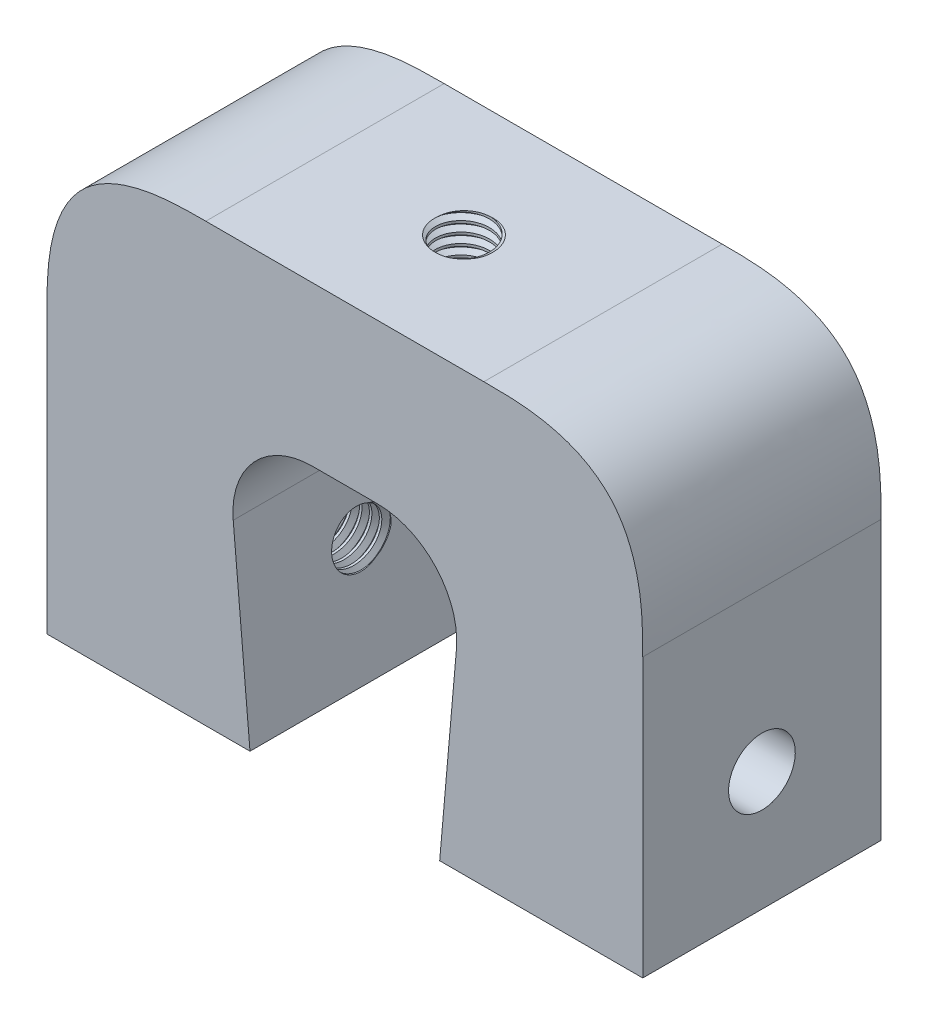
SolidWorks part; units mm, degrees
ref_plane "Front Plane" through (0, 0, 0) normal (0, 0, 1) x (1, 0, 0)
ref_plane "Top Plane" through (0, 0, 0) normal (0, 1, 0) x (1, 0, 0)
ref_plane "Right Plane" through (0, 0, 0) normal (1, 0, 0) x (0, 0, -1)
sketch "Sketch2" plane through (0, 0, 0) normal (0, 0, 1) x (1, 0, 0)
  line L0 (11.9379, -27.5) -> (37.5, -27.5)
  line L1 (-37.5, 27.5) -> (37.5, 27.5)
  line L2 (-37.5, 27.5) -> (-37.5, -27.5)
  line L3 (-37.5, -27.5) -> (-11.9379, -27.5)
  line L4 (37.5, 27.5) -> (37.5, -27.5)
  line L5 (-37.5, 27.5) -> (37.5, -27.5) construction
  line L6 (-37.5, -27.5) -> (37.5, 27.5) construction
  line L8 (-11.9379, -27.5) -> (-15, 7.5)
  line L9 (-15, 7.5) -> (15, 7.5)
  line L10 (11.9379, -27.5) -> (15, 7.5)
  line L13 (0, 0) -> (0, 7.5) construction
  point P0 (0, 0)
  dimension "D1" = 5
  dimension "D2" = 35
  dimension "D3" = 55
  dimension "D4" = 75
  dimension "D5" = 30
extrude "Boss-Extrude1" add sketch "Sketch2" along normal blind 30
fillet "Fillet2" radius 20 2 edges at (37.5, 27.5, 15) (-37.5, 27.5, 15) curvature continuous yes
fillet "Fillet3" radius 10 2 edges at (15, 7.5, 15) (-15, 7.5, 15)
sketch "Sketch13" plane through (37.5, 0, 0) normal (1, 0, 0) x (0, 0, -1)
  line L0 (-15, -27.5) -> (-15, -12.5) construction
  line L1 (-30, -27.5) -> (0, -27.5) construction
  circle A0 centre (-15, -12.5) radius 3.4
  dimension "D1" = 6.8
  dimension "D2" = 15
extrude "Cut-Extrude1" cut sketch "Sketch13" against normal up to next
sketch "Sketch14" plane through (37.5, 0, 0) normal (1, 0, 0) x (0, 0, -1)
  circle A0 centre (-15, -12.5) radius 4.2
  dimension "D1" = 8.4
extrude "Cut-Extrude2" cut sketch "Sketch14" against normal blind 15
thread "Thread2" pitch 1.25 method cut trim with start face yes trim with end face yes profile "Thread Profile2" start angle 0, offset 5, length 20, pitch 1.25, diameter 6.8
ref_plane "Plane2" through (27.5, -12.5, 18.4) normal (0, -1, 0) x (0, 0, 1)
sketch "Thread Profile2" plane through (27.5, -12.5, 18.4) normal (0, -1, 0) x (0, 0, 1)
  line L0 (0, 0) -> (0, 1.25) construction
  line L1 (0, 0) -> (0.6766, 0.3906)
  line L2 (0.6766, 0.3906) -> (0.6766, 0.5469)
  line L3 (0.6766, 0.5469) -> (0, 0.9375)
  line L4 (0.6766, 0.4687) -> (0, 0.4687) construction
  line L11 (0, 0) -> (0, 0.9375)
  point P2 (0, 0)
  dimension "Pitch" = 1.25
  dimension "Profile_Angle" = 60
  dimension "Profile_Land" = 0.1562
  dimension "Profile_Height" = 0.6766
mirror "Mirror2" about plane through (0, 0, 0) normal (1, 0, 0) of "Cut-Extrude2", "Cut-Extrude1"
thread "Thread3" pitch 1.25 method cut trim with start face yes trim with end face yes profile "Thread Profile3" start angle 0, offset 5, length 20, pitch 1.25, diameter 6.8
ref_plane "Plane3" through (-27.5, -12.5, 11.6) normal (0, -1, 0) x (0, 0, -1)
sketch "Thread Profile3" plane through (-27.5, -12.5, 11.6) normal (0, -1, 0) x (0, 0, -1)
  line L0 (0, 0) -> (0, 1.25) construction
  line L1 (0, 0) -> (0.6766, 0.3906)
  line L2 (0.6766, 0.3906) -> (0.6766, 0.5469)
  line L3 (0.6766, 0.5469) -> (0, 0.9375)
  line L4 (0.6766, 0.4687) -> (0, 0.4687) construction
  line L11 (0, 0) -> (0, 0.9375)
  point P2 (0, 0)
  dimension "Pitch" = 1.25
  dimension "Profile_Angle" = 60
  dimension "Profile_Land" = 0.1562
  dimension "Profile_Height" = 0.6766
sketch "Sketch21" plane through (0, 27.5, 0) normal (0, 1, 0) x (1, 0, 0)
  line L0 (0, 0) -> (0, -30) construction
  line L1 (17.5, 0) -> (-17.5, 0) construction
  line L2 (17.5, -30) -> (-17.5, -30) construction
  circle A0 centre (0, -15) radius 3.4
  point P8 (0, -15)
  dimension "D1" = 6.8
extrude "Cut-Extrude3" cut sketch "Sketch21" against normal blind 15
thread "Thread4" pitch 1.25 method cut trim with start face yes trim with end face yes profile "Thread Profile4" start angle 0, offset 5, length 0, pitch 1.25, diameter 6.8
ref_plane "Plane4" through (-3.4, 32.5, 15) normal (0, 0, 1) x (-1, 0, 0)
sketch "Thread Profile4" plane through (-3.4, 32.5, 15) normal (0, 0, 1) x (-1, 0, 0)
  line L0 (0, 0) -> (0, 1.25) construction
  line L1 (0, 0) -> (0.6766, 0.3906)
  line L2 (0.6766, 0.3906) -> (0.6766, 0.5469)
  line L3 (0.6766, 0.5469) -> (0, 0.9375)
  line L4 (0.6766, 0.4687) -> (0, 0.4687) construction
  line L11 (0, 0) -> (0, 0.9375)
  point P2 (0, 0)
  dimension "Pitch" = 1.25
  dimension "Profile_Angle" = 60
  dimension "Profile_Land" = 0.1562
  dimension "Profile_Height" = 0.6766
